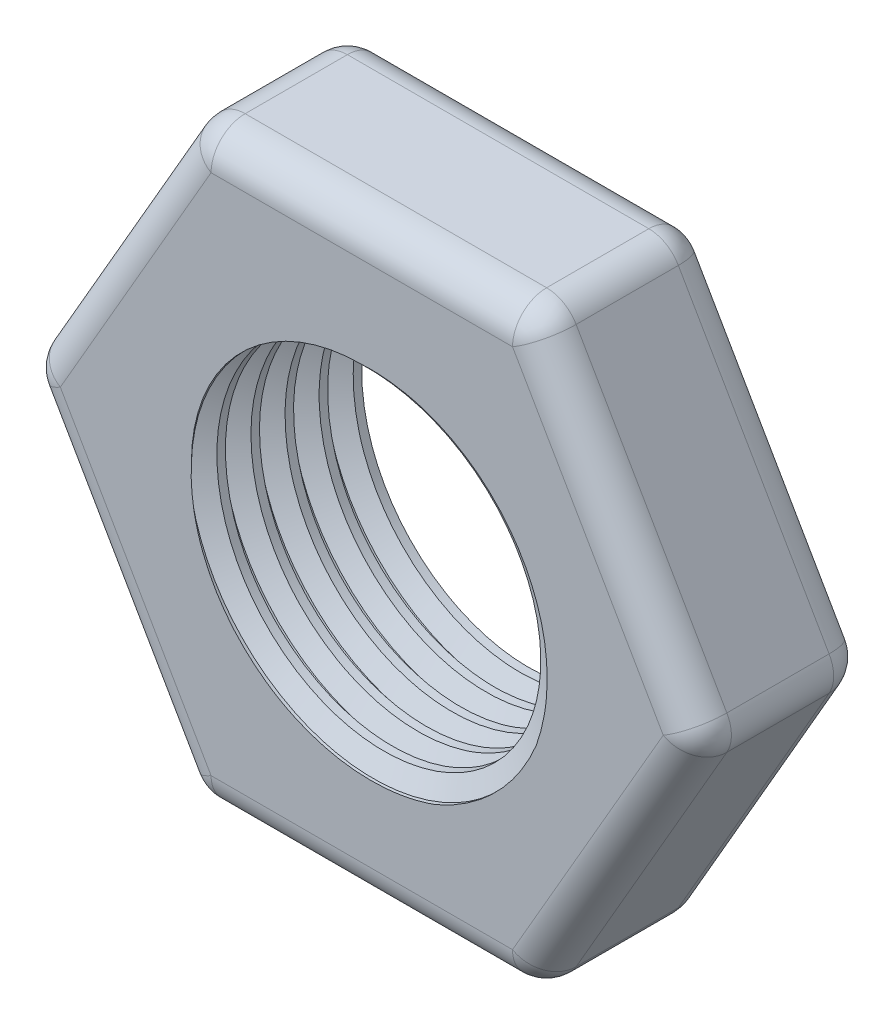
SolidWorks part; units mm, degrees
ref_plane "Plan de face" through (0, 0, 0) normal (0, 0, 1) x (1, 0, 0)
ref_plane "Plan de dessus" through (0, 0, 0) normal (0, 1, 0) x (1, 0, 0)
ref_plane "Plan de droite" through (0, 0, 0) normal (1, 0, 0) x (0, 0, -1)
sketch "Esquisse1" plane through (0, 0, 0) normal (0, 0, 1) x (1, 0, 0)
  line L1 (10, 0) -> (5, 8.6603)
  line L2 (5, 8.6603) -> (-5, 8.6603)
  line L3 (-5, 8.6603) -> (-10, 0)
  line L4 (-10, 0) -> (-5, -8.6603)
  line L5 (-5, -8.6603) -> (5, -8.6603)
  line L6 (5, -8.6603) -> (10, 0)
  circle A0 centre (0, 0) radius 8.6603 construction
  circle A1 centre (0, 0) radius 5
  dimension "D2" = 10
  dimension "D1" = 20
extrude "Boss.-Extru.1" add sketch "Esquisse1" along normal blind 5
thread "Filetage1" pitch 1 method cut profile "Profil de filetage1" start angle 0, offset 1, length 0, pitch 1, diameter 10
ref_plane "Plan1" through (-5, 0, 6) normal (0, -1, 0) x (-1, 0, 0)
sketch "Profil de filetage1" plane through (-5, 0, 6) normal (0, -1, 0) x (-1, 0, 0)
  line L0 (0, 0) -> (0, 1) construction
  line L1 (0, 0) -> (0.5413, 0.3125)
  line L2 (0.5413, 0.3125) -> (0.5413, 0.4375)
  line L3 (0.5413, 0.4375) -> (0, 0.75)
  line L4 (0.5413, 0.375) -> (0, 0.375) construction
  line L11 (0, 0) -> (0, 0.75)
  point P2 (0, 0)
  dimension "Pitch" = 1
  dimension "Profile_Angle" = 60
  dimension "Profile_Land" = 0.125
  dimension "Profile_Height" = 0.5413
fillet "Congé1" radius 1 18 edges at (7.5, -4.3301, 5) (7.5, -4.3301, 0) (0, -8.6603, 5) (5, -8.6603, 2.5) (0, -8.6603, 0) (10, 0, 2.5) (7.5, 4.3301, 5) (7.5, 4.3301, 0) (-7.5, -4.3301, 5) (-5, -8.6603, 2.5) (-7.5, -4.3301, 0) (-7.5, 4.3301, 5) (-10, 0, 2.5) (-7.5, 4.3301, 0) (5, 8.6603, 2.5) (0, 8.6603, 5) (-5, 8.6603, 2.5) (0, 8.6603, 0)
